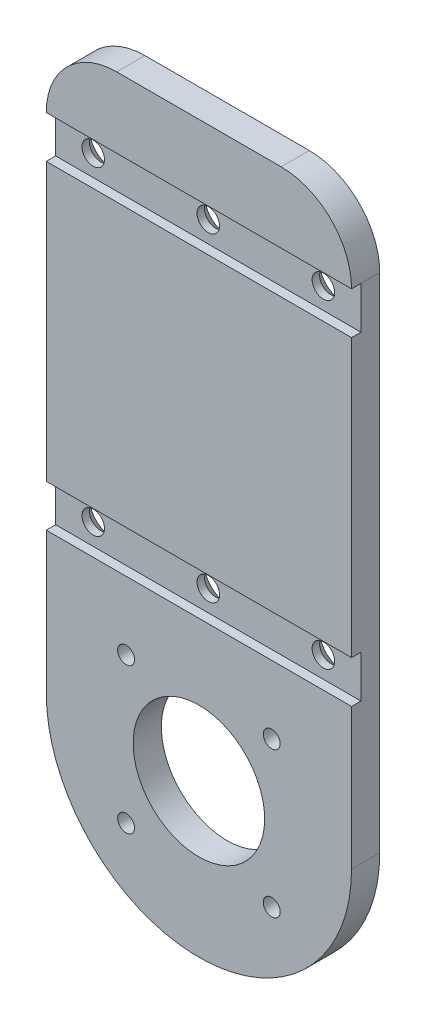
SolidWorks part; units mm, degrees
ref_plane "Front Plane" through (0, 0, 0) normal (0, 0, 1) x (1, 0, 0)
ref_plane "Top Plane" through (0, 0, 0) normal (0, 1, 0) x (1, 0, 0)
ref_plane "Right Plane" through (0, 0, 0) normal (1, 0, 0) x (0, 0, -1)
sketch "Sketch1" plane through (0, 0, 0) normal (0, 0, 1) x (1, 0, 0)
  line L1 (-32.5, -95) -> (32.5, -95)
  line L2 (-32.5, -95) -> (-32.5, 95)
  line L3 (-32.5, 95) -> (32.5, 95)
  line L4 (32.5, -95) -> (32.5, 95)
  line L5 (-32.5, -95) -> (32.5, 95) construction
  line L6 (-32.5, 95) -> (32.5, -95) construction
  line L7 (15.5, -110.5) -> (-15.5, -110.5)
  line L8 (15.5, -110.5) -> (15.5, -79.5)
  line L9 (15.5, -79.5) -> (-15.5, -79.5)
  line L10 (-15.5, -110.5) -> (-15.5, -79.5)
  line L11 (15.5, -110.5) -> (-15.5, -79.5) construction
  line L12 (15.5, -79.5) -> (-15.5, -110.5) construction
  circle A0 centre (0, -95) radius 32.5
  circle A1 centre (0, -95) radius 42 construction
  circle A2 centre (0, -95) radius 14
  point P0 (0, 0)
  point P14 (0, -127.5)
  dimension "D1" = 84
  dimension "D4" = 28
  dimension "D2" = 31
  dimension "D3" = 31
  dimension "D5" = 65
  dimension "D6" = 190
  dimension "D7" = 222.5
extrude "Boss-Extrude1" add sketch "Sketch1" along normal blind 6 contours A0 L4 L3 L2 | L1 A0 L10 L9 L8 | L1 A0 L8 L7 L10 | A2 L1 L10 L7 L8 | A2 L1 L8 L9 L10 region at (0, -78.7429, 0) region at (0, 12.6028, 0) region at (0, -111.2571, 0) region at (-15.1534, -87.25, 0) region at (-14.75, -95.3466, 0)
hole_wizard "M3 Clearance Hole1" positions "Sketch2" profile "Sketch3" hole size "M3" standard "ANSI Metric"
sketch "Sketch2" plane through (0, 0, 0) normal (0, 0, -1) x (-1, 0, 0)
  point P0 (-15.5, -110.5)
  point P3 (15.5, -110.5)
  point P6 (15.5, -79.5)
  point P9 (-15.5, -79.5)
sketch "Sketch3" plane through (15.5, -110.5, 0) normal (1, 0, 0) x (0, 1, 0)
  line L0 (0, 0) -> (0, 7.0815)
  line L1 (0, 7.0815) -> (1.8, 6)
  line L2 (1.8, 6) -> (1.8, 0)
  line L5 (1.8, 0) -> (0, 0)
  line L10 (0, 7.0815) -> (-1.8, 6) construction
  line L11 (0, -6.35) -> (0, 107.95) construction
  dimension "Hole Dia." = 3.6
  dimension "Hole Depth" = 6
  dimension "Drill Angle" = 118
fillet "Fillet1" radius 15 2 edges at (-32.5, 95, 3) (32.5, 95, 3)
sketch "Sketch4" plane through (0, 0, 6) normal (0, 0, 1) x (1, 0, 0)
  line L0 (32.5, -95) -> (32.5, 80) construction
  line L1 (32.5, -65) -> (-32.5, -65)
  line L2 (32.5, -65) -> (32.5, -56)
  line L3 (32.5, -56) -> (-32.5, -56)
  line L4 (-32.5, -65) -> (-32.5, -56)
  line L5 (-32.5, -95) -> (-32.5, 80) construction
  line L6 (0, 12) -> (0, 3)
  line L7 (32.5, 80) -> (-32.5, 80)
  line L8 (32.5, 80) -> (32.5, 71)
  line L9 (32.5, 71) -> (-32.5, 71)
  line L10 (-32.5, 80) -> (-32.5, 71)
  line L11 (-32.5, 12) -> (32.5, 12)
  line L12 (-32.5, 12) -> (-32.5, 3)
  line L13 (-32.5, 3) -> (32.5, 3)
  line L14 (32.5, 12) -> (32.5, 3)
  point P20 (0, 7.5)
  line M15 (-32.5, 80) -> (-32.5, -95)
  line M17 (32.5, -95) -> (32.5, 80)
  dimension "D1" = 9
  dimension "D2" = 9
  dimension "D3" = 9
  dimension "D4" = 30
  dimension "D5" = 127
  dimension "D6" = 63.5
extrude "Cut-Extrude1" cut sketch "Sketch4" against normal blind 2 contours L9 L7 M17 M15 | L13 L6 L11 M15 | L6 L13 L11 M17 | L3 L1 M17 M15 region at (0, -60.5, 6) region at (16.25, 7.5, 6) region at (-16.25, 7.5, 6) region at (0, 75.5, 6)
hole_wizard "M4 Clearance Hole1" positions "Sketch5" profile "Sketch6" hole size "M4" standard "ANSI Metric"
sketch "Sketch5" plane through (0, 0, 4) normal (0, 0, 1) x (1, 0, 0)
  line L0 (-32.5, 75.5) -> (32.5, 75.5)
  line L1 (-32.5, 80) -> (-32.5, 71) construction
  line L2 (32.5, 71) -> (32.5, 80) construction
  line L4 (-32.5, 7.5) -> (32.5, 7.5)
  line L5 (-32.5, 12) -> (-32.5, 3) construction
  line L6 (32.5, 3) -> (32.5, 12) construction
  line L8 (-32.5, -60.5) -> (32.5, -60.5)
  line L9 (-32.5, -56) -> (-32.5, -65) construction
  line L10 (32.5, -65) -> (32.5, -56) construction
  point P24 (-24.5, 75.5)
  point P26 (24.5, 75.5)
  point P28 (0, 75.5)
  point P30 (-24.5, 7.5)
  point P32 (0, 7.5)
  point P34 (24.5, 7.5)
  point P36 (24.5, -60.5)
  point P38 (0, -60.5)
  point P40 (-24.5, -60.5)
  dimension "D1" = 8
  dimension "D2" = 8
sketch "Sketch6" plane through (-24.5, -60.5, 4) normal (1, 0, 0) x (0, -1, 0)
  line L0 (0, 0) -> (0, 7.4421)
  line L1 (0, 7.4421) -> (2.4, 6)
  line L2 (2.4, 6) -> (2.4, 0)
  line L5 (2.4, 0) -> (0, 0)
  line L10 (0, 7.4421) -> (-2.4, 6) construction
  line L11 (0, -6.35) -> (0, 107.95) construction
  dimension "Hole Dia." = 4.8
  dimension "Hole Depth" = 6
  dimension "Drill Angle" = 118
chamfer "Chamfer1" distance 2.4 13 edges at (13.7, -110.5, 0) (-17.3, -110.5, 0) (-17.3, -79.5, 0) (13.7, -79.5, 0) (-22.1, 75.5, 0) (2.4, 75.5, 0) (26.9, 75.5, 0) (26.9, 7.5, 0) (2.4, 7.5, 0) (-22.1, 7.5, 0) (-22.1, -60.5, 0) (2.4, -60.5, 0) (26.9, -60.5, 0)
sketch "Sketch7" plane through (0, 0, 6) normal (0, 0, 1) x (1, 0, 0)
  line L0 (32.5, 12) -> (32.5, 71) construction
  line L1 (-32.5, 27) -> (32.5, 27)
  line L2 (-32.5, 27) -> (-32.5, 105)
  line L3 (-32.5, 105) -> (32.5, 105)
  line L4 (32.5, 27) -> (32.5, 105)
  line L5 (-17.5, 95) -> (17.5, 95) construction
  line L6 (-32.5, 12) -> (-32.5, 71) construction
  line L7 (-32.5, 12) -> (32.5, 12) construction
  dimension "D1" = 10
  dimension "D2" = 15
extrude "Cut-Extrude3" cut sketch "Sketch7" against normal through all
fillet "Fillet2" radius 15 2 edges at (32.5, 27, 3) (-32.5, 27, 3)
